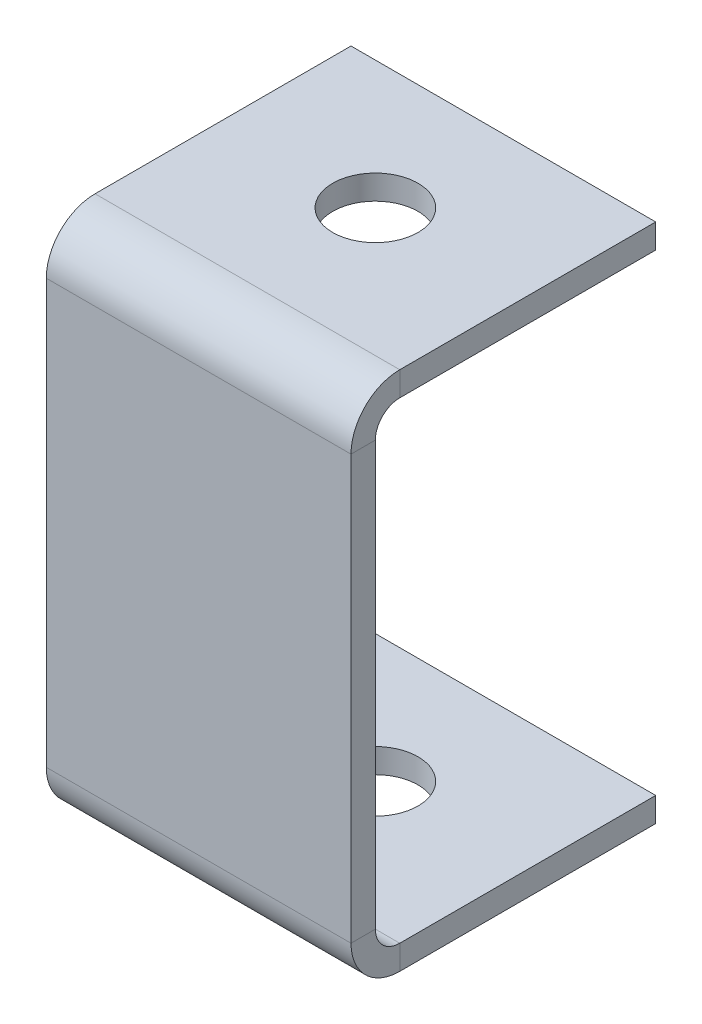
SolidWorks part; units mm, degrees
note: The reader was unsure of these and kept them because the rebuilt part matched: flange length of "Edge-Flange1".
material "2024-O"
ref_plane "Front Plane" through (0, 0, 0) normal (0, 0, 1) x (1, 0, 0)
ref_plane "Top Plane" through (0, 0, 0) normal (0, 1, 0) x (1, 0, 0)
ref_plane "Right Plane" through (0, 0, 0) normal (1, 0, 0) x (0, 0, -1)
sketch "Sketch1" plane through (0, 0, 0) normal (0, 0, 1) x (1, 0, 0)
  line L1 (12.5, -21.375) -> (-12.5, -21.375)
  line L2 (12.5, -21.375) -> (12.5, 21.375)
  line L3 (12.5, 21.375) -> (-12.5, 21.375)
  line L4 (-12.5, -21.375) -> (-12.5, 21.375)
  line L5 (12.5, -21.375) -> (-12.5, 21.375) construction
  line L6 (12.5, 21.375) -> (-12.5, -21.375) construction
  point P0 (0, 0)
  dimension "D1" = 25
  dimension "D2" = 42.75
base flange "Base-Flange2" sketch "Sketch1" thickness 2 reverse thickness direction no parameters "D1"=0.7366
edge flange "Edge-Flange1" sketch "Sketch12" flange angle 90 flange length 25 flange position material inside bend radius 2 thickness 2 relief rectangular parameters "D6"=10
sketch "Sketch12" plane through (0, -21.375, -2) normal (0, 1, 0) x (1, 0, 0)
  line L2 (-12.5, 0) -> (-12.5, 23)
  line L3 (-12.5, 23) -> (12.5, 23)
  line L4 (12.5, 23) -> (12.5, 0)
  line L9 (12.5, 0) -> (-12.5, 0) construction
  line L10 (12.5, 0) -> (-12.5, 0)
bend "EdgeBend1" bend radius 2 bend angle 90 parameters "D5"=1
sketch "Sketch13" plane through (0, 0, -2) normal (0, 0, -1) x (-1, 0, 0)
  line L0 (-12.5, -19.375) -> (12.5, -19.375) construction
  circle A0 centre (0, 35.625) radius 3.5
  dimension "D1" = 7
  dimension "D2" = 55
extrude "Cut-Extrude1" [suppressed] cut sketch "Sketch13" against normal through all
sketch "Sketch14" plane through (0, -19.375, 0) normal (0, 1, 0) x (1, 0, 0)
  line L1 (-12.5, 2) -> (12.5, 2) construction
  circle A0 centre (0, 14.5) radius 3.5
  dimension "D1" = 7
  dimension "D3" = 12.5
extrude "Cut-Extrude2" cut sketch "Sketch14" against normal through all normal cut yes
fillet "Fillet1" [suppressed] radius 10.4167
mirror "Mirror1" about plane through (0, 0, 0) normal (0, 1, 0) of "Cut-Extrude2", "Edge-Flange1"
bend "MirrorBend1" bend radius 2 bend angle 90 parameters "D5"=2
sketch "Bend-Lines3" [suppressed] plane through (0, 0, 0) normal (0, 1, 0) x (1, 0, 0)
sketch "Bounding-Box3" [suppressed] plane through (0, 0, 0) normal (0, 1, 0) x (1, 0, 0)
sheet metal parameters "Sheet-Metal2" thickness 2 parameters "D1"=0.7366
flat pattern "Flat-Pattern2" [suppressed]
sketch "Bend-Lines4" plane through (0, 0, 0) normal (0, 1, 0) x (1, 0, 0)
sketch3d "Bounding-Box4" [suppressed]
  line L0 (15, 35, 0) -> (15, -35, 0) construction
  line L1 (-15, 35, 0) -> (-15, -35, 0) construction
  line L2 (15, 35, 0) -> (-15, 35, 0) construction
  line L3 (15, -35, 0) -> (-15, -35, 0) construction
sheet metal parameters "Sheet-Metal3" thickness 2 parameters "D1"=0.7366
flat pattern "Flat-Pattern2"
sketch "Bend-Lines4" plane through (0, 0, 0) normal (0, 0, 1) x (1, 0, 0)
  line L0 (-12.5, -19.8562) -> (12.5, -19.8562) construction
  line L1 (-12.5, -19.8562) -> (12.5, -19.8562) construction
sketch3d "Bounding-Box4" [suppressed]
  line L0 (12.5, 21.5, 0) -> (12.5, -48.2124, 0) construction
  line L1 (-12.5, 21.5, 0) -> (-12.5, -48.2124, 0) construction
  line L2 (12.5, 21.5, 0) -> (-12.5, 21.5, 0) construction
  line L3 (12.5, -48.2124, 0) -> (-12.5, -48.2124, 0) construction
bend of the flat pattern "Flatten-<EdgeBend1>1"
sheet metal parameters "Sheet-Metal4" thickness 2 parameters "D1"=0.7366
flat pattern "Flat-Pattern2"
sketch "Bend-Lines4" plane through (0, 0, 0) normal (0, 0, 1) x (1, 0, 0)
  line L0 (-12.5, -33.3562) -> (12.5, -33.3562) construction
  line L1 (-12.5, -33.3562) -> (12.5, -33.3562) construction
sketch3d "Bounding-Box4" [suppressed]
  line L0 (12.5, 35, 0) -> (12.5, -61.7124, 0) construction
  line L1 (-12.5, 35, 0) -> (-12.5, -61.7124, 0) construction
  line L2 (12.5, 35, 0) -> (-12.5, 35, 0) construction
  line L3 (12.5, -61.7124, 0) -> (-12.5, -61.7124, 0) construction
bend of the flat pattern "Flatten-<EdgeBend1>1"
sheet metal parameters "Sheet-Metal5" thickness 2 parameters "D1"=0.7366
flat pattern "Flat-Pattern2"
sketch "Bend-Lines4" plane through (0, 0, 0) normal (0, 0, 1) x (1, 0, 0)
  line L0 (-12.5, -33.3562) -> (12.5, -33.3562) construction
  line L1 (-12.5, -33.3562) -> (12.5, -33.3562) construction
sketch3d "Bounding-Box4" [suppressed]
  line L0 (12.5, -61.7123, 0) -> (12.5, 35, 0) construction
  line L1 (-12.5, -61.7123, 0) -> (-12.5, 35, 0) construction
  line L2 (12.5, -61.7123, 0) -> (-12.5, -61.7123, 0) construction
  line L3 (12.5, 35, 0) -> (-12.5, 35, 0) construction
bend of the flat pattern "Flatten-<EdgeBend1>1"
sheet metal parameters "Sheet-Metal6" thickness 2 parameters "D1"=0.7366
flat pattern "Flat-Pattern2"
sketch "Bend-Lines4" plane through (0, 0, 0) normal (0, 0, 1) x (1, 0, 0)
  line L0 (-12.5, -19.7312) -> (12.5, -19.7312) construction
  line L1 (-12.5, -19.7312) -> (12.5, -19.7312) construction
  line L2 (12.5, 19.7312) -> (-12.5, 19.7312) construction
  line L3 (12.5, 19.7312) -> (-12.5, 19.7312) construction
sketch3d "Bounding-Box4" [suppressed]
  line L0 (12.5, 43.0874, 0) -> (12.5, -43.0874, 0) construction
  line L1 (-12.5, 43.0874, 0) -> (-12.5, -43.0874, 0) construction
  line L2 (12.5, 43.0874, 0) -> (-12.5, 43.0874, 0) construction
  line L3 (12.5, -43.0874, 0) -> (-12.5, -43.0874, 0) construction
bend of the flat pattern "Flatten-<EdgeBend1>1"
bend of the flat pattern "Flatten-<MirrorBend1>1"
equation "\"Altura do L\"= 70"
equation "\"largura do L\"= 25"
equation "\"D1@Sketch1\"=25"
equation "\"D7@Edge-Flange1\"=\"largura do L\""
equation "\"D1@EdgeBend1\"=\"Thickness\""
equation "\"diametro do furo\"= 7"
equation "\"D1@Sketch13\"=\"diametro do furo\""
equation "\"D1@Sketch14\"=\"diametro do furo\""
equation "\"D3@Sketch14\"=\"largura do L\"/2"
equation "\"D1@Fillet1\"=(\"largura do L\"*(5/6))/2"
equation "\"D2@Sketch1\" = \"Altura do L\""
